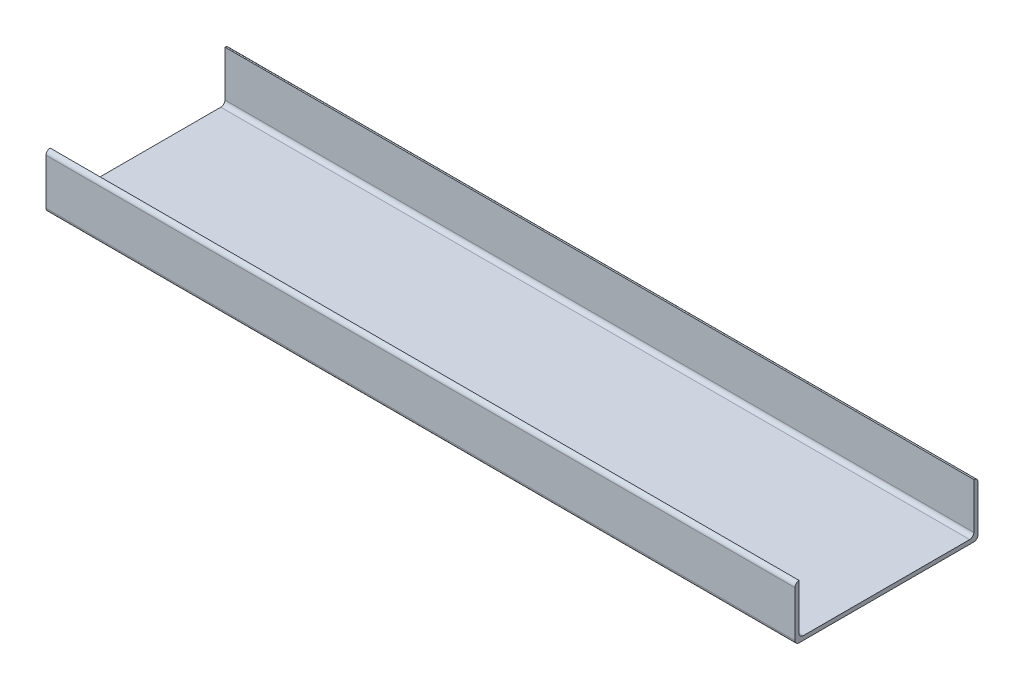
SolidWorks part; units mm, degrees
ref_plane "Front Plane" through (0, 0, 0) normal (0, 0, 1) x (1, 0, 0)
ref_plane "Top Plane" through (0, 0, 0) normal (0, 1, 0) x (1, 0, 0)
ref_plane "Right Plane" through (0, 0, 0) normal (1, 0, 0) x (0, 0, -1)
sketch "Sketch1" plane through (0, 0, 0) normal (0, 1, 0) x (1, 0, 0)
  line L0 (-90, 22) -> (90, -22) construction
  line L1 (-90, 22) -> (90, 22)
  line L2 (-90, 22) -> (-90, -22)
  line L3 (-90, -22) -> (90, -22)
  line L4 (90, 22) -> (90, -22)
  line L5 (90, -22) -> (91.079, -20.2017) construction
  dimension "D1" = 44
  dimension "D2" = 180
extrude "Boss-Extrude1" add sketch "Sketch1" along normal blind 1
sketch "Sketch2" plane through (0, 1, 0) normal (0, 1, 0) x (1, 0, 0)
  line L0 (90, -22) -> (90, 22) construction
  line L1 (-90, 22) -> (90, 22)
  line L2 (-90, 22) -> (-90, 21)
  line L3 (-90, 21) -> (90, 21)
  line L4 (90, 22) -> (90, 21)
  line L6 (-90, -22) -> (90, -22)
  line L7 (-90, -22) -> (-90, -21)
  line L8 (-90, -21) -> (90, -21)
  line L9 (90, -22) -> (90, -21)
  dimension "D1" = 1
  dimension "D2" = 1
extrude "Boss-Extrude2" add sketch "Sketch2" along normal blind 12
fillet "Fillet1" radius 1 1 edges at (0, 13, 22) type face fillet first side face at (0, 13, 21.5) second side face at (0, 6.5, 22)
fillet "Fillet2" radius 1 1 edges at (0, 13, -22) type face fillet first side face at (0, 13, -21.5) second side face at (0, 6.5, -22)
fillet "Fillet3" radius 1 1 edges type face fillet first side face at (-22.5, 10, -21) second side face at (-22.5, 1, 0)
fillet "Fillet4" radius 1 1 edges at (0, 1, 21) type face fillet first side face at (0, 7, 21) second side face at (0, 1, 0.5)
fillet "Fillet5" radius 1 1 edges at (0, 0, 22) type face fillet first side face at (0, 6, 22) second side face at (0, 0, 0)
fillet "Fillet6" radius 1 1 edges at (0, 0, -22) type face fillet first side face at (0, 6, -22) second side face at (0, 0, -0.5)
